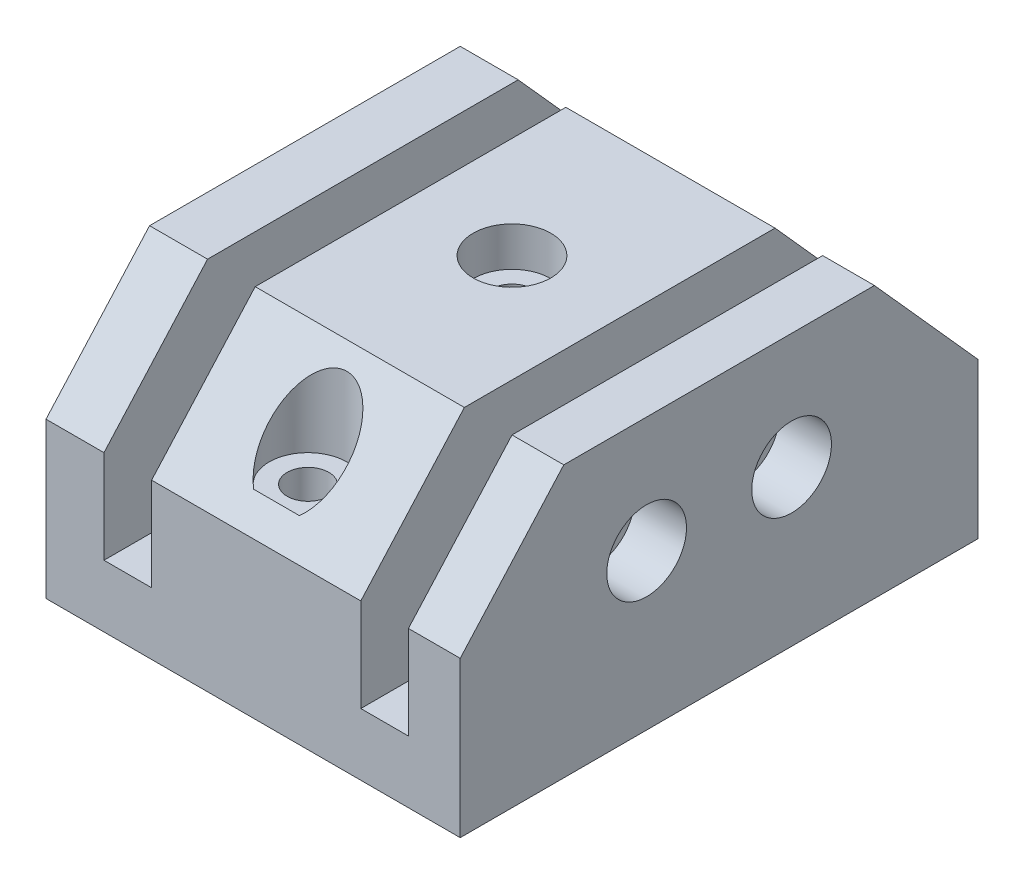
SolidWorks part; units mm, degrees
ref_plane "Front Plane" through (0, 0, 0) normal (0, 0, 1) x (1, 0, 0)
ref_plane "Top Plane" through (0, 0, 0) normal (0, 1, 0) x (1, 0, 0)
ref_plane "Right Plane" through (0, 0, 0) normal (1, 0, 0) x (0, 0, -1)
sketch "Sketch1" plane through (0, 0, 0) normal (1, 0, 0) x (0, 0, -1)
  line L1 (0, 0) -> (63.5, 0)
  line L2 (0, 0) -> (0, 6.35)
  line L3 (0, 6.35) -> (63.5, 6.35)
  line L4 (63.5, 0) -> (63.5, 6.35)
  dimension "D1" = 6.35
  dimension "D2" = 63.5
extrude "Boss-Extrude1" add sketch "Sketch1" against normal blind 50.8
sketch "Sketch2" plane through (0, 0, 0) normal (1, 0, 0) x (0, 0, -1)
  line L0 (0, 6.35) -> (0, 19.05)
  line L1 (0, 19.05) -> (12.7, 33.249)
  line L2 (12.7, 33.249) -> (50.8, 33.249)
  line L3 (50.8, 33.249) -> (63.5, 19.05)
  line L4 (63.5, 19.05) -> (63.5, 6.35)
  line L5 (63.5, 6.35) -> (0, 6.35)
  point P7 (31.75, 33.249)
  point P10 (31.75, 6.35)
  dimension "D1" = 38.1
  dimension "D2" = 12.7
  dimension "D3" = 12.7
  dimension "D4" = 19.05
  dimension "D5" = 19.05
extrude "Boss-Extrude2" add sketch "Sketch2" against normal blind 50.8
sketch "Sketch10" plane through (0, 0, -63.5) normal (0, 0, -1) x (-1, 0, 0)
  line L1 (50.8, 33.249) -> (0, 33.249) construction
  line L3 (6.35, 7.62) -> (6.35, 33.249)
  line L4 (6.35, 33.249) -> (12.192, 33.249)
  line L5 (12.192, 7.62) -> (12.192, 33.249)
  line L6 (6.35, 7.62) -> (12.192, 7.62)
  line L8 (50.8, 0) -> (0, 0) construction
  point P11 (12.192, 7.62)
  dimension "D1" = 7.62
  dimension "D2" = 5.842
  dimension "D3" = 6.35
extrude "Cut-Extrude1" cut sketch "Sketch10" against normal through all
pattern_linear "LPattern3" count 2 spacing 31.496 along (-1, 0, 0) of "Cut-Extrude1"
sketch "Sketch11" plane through (0, 0, 0) normal (1, 0, 0) x (0, 0, -1)
  circle A0 centre (22.86, 19.05) radius 4.8895
  circle A1 centre (22.86, 19.05) radius 7.9375 construction
  circle A2 centre (40.64, 19.05) radius 4.8895
  circle A3 centre (40.64, 19.05) radius 7.9375 construction
  dimension "D1" = 9.779
  dimension "D3" = 15.875
  dimension "D4" = 9.779
  dimension "D6" = 15.875
  dimension "D2" = 10.16
  dimension "D5" = 10.16
extrude "Cut-Extrude2" cut sketch "Sketch11" against normal through all
sketch "Sketch14" plane through (0, 33.249, 0) normal (0, 1, 0) x (1, 0, 0)
  line L3 (-37.846, 12.7) -> (-37.846, 50.8) construction
  point P0 (-25.4, 31.75)
  point P4 (-37.846, 31.75)
  dimension "D1" = 12.446
hole_wizard "CBORE for #10 Socket Head Cap Screw1" positions "Sketch15" profile "Sketch16" counterbore size "#10" standard "ANSI Inch" end condition up to next
sketch "Sketch15" plane through (0, 33.249, 0) normal (0, 1, 0) x (1, 0, 0)
  point P0 (-25.4, 31.75)
sketch "Sketch16" plane through (-25.4, 33.249, -31.75) normal (1, 0, 0) x (0, 0, 1)
  line L0 (0, 0) -> (0, 33.249)
  line L1 (0, 33.249) -> (2.5527, 33.249)
  line L3 (2.5527, 33.249) -> (2.5527, 4.826)
  line L4 (2.5527, 4.826) -> (4.7625, 4.826)
  line L5 (4.7625, 4.826) -> (4.7625, 0)
  line L7 (4.7625, 0) -> (0, 0)
  line L11 (0, -6.35) -> (0, 107.95) construction
  dimension "Thru Hole Dia." = 5.1054
  dimension "Thru Hole Depth" = 33.249
  dimension "C'Bore Dia." = 9.525
  dimension "C'Bore Depth" = 4.826
sketch "Sketch17" plane through (0, 40.0201, -44.7438) normal (0, 0.6667, -0.7454) x (-1, 0, 0)
  line L0 (12.192, -28.1343) -> (12.192, -9.0843) construction
  line L1 (37.846, -9.0843) -> (12.192, -9.0843) construction
  point P0 (25.019, -18.6093)
  point P4 (12.192, -18.6093)
  point P7 (25.019, -9.0843)
sketch "Sketch18" plane through (0, 8.4667, 9.466) normal (0, 0.6667, 0.7454) x (1, 0, 0)
  line L0 (-12.192, 33.249) -> (-12.192, 14.199) construction
  line L1 (-37.846, 33.249) -> (-12.192, 33.249) construction
  point P0 (-25.019, 23.724)
  point P1 (-25.019, 23.724)
  point P4 (-12.192, 23.724)
  point P7 (-25.019, 33.249)
ref_plane "Plane2" through (0, 33.02, 0) normal (0, -1, 0) x (-1, 0, 0)
hole_wizard "CBORE for #10 Socket Head Cap Screw3" positions "Sketch24" profile "Sketch25" counterbore size "#10" standard "ANSI Inch" end condition up to next
sketch "Sketch24" plane through (0, 33.02, 0) normal (0, -1, 0) x (-1, 0, 0)
  point P0 (25.019, 6.35)
  point P2 (25.019, 57.15)
sketch "Sketch25" plane through (-25.019, 33.02, -6.35) normal (1, 0, 0) x (0, 0, 1)
  line L0 (0, 0) -> (0, 33.02)
  line L1 (0, 33.02) -> (2.5527, 33.02)
  line L3 (2.5527, 33.02) -> (2.5527, 11.176)
  line L4 (2.5527, 11.176) -> (4.7625, 11.176)
  line L5 (4.7625, 11.176) -> (4.7625, 0)
  line L7 (4.7625, 0) -> (0, 0)
  line L11 (0, -6.35) -> (0, 107.95) construction
  dimension "Thru Hole Dia." = 5.1054
  dimension "Thru Hole Depth" = 33.02
  dimension "C'Bore Dia." = 9.525
  dimension "C'Bore Depth" = 11.176
ref_plane "midplane" through (0, 0, -31.75) normal (0, 0, -1) x (-1, 0, 0)
